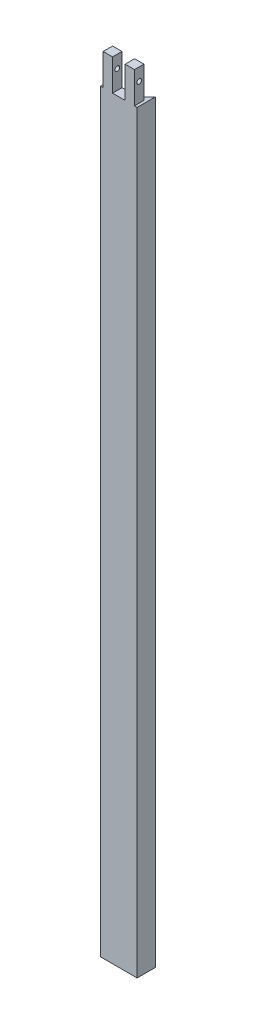
SolidWorks part; units mm, degrees
ref_plane "Front Plane" through (0, 0, 0) normal (0, 0, 1) x (1, 0, 0)
ref_plane "Top Plane" through (0, 0, 0) normal (0, 1, 0) x (1, 0, 0)
ref_plane "Right Plane" through (0, 0, 0) normal (1, 0, 0) x (0, 0, -1)
sketch "Sketch2" plane through (0, 0, 0) normal (0, 0, 1) x (1, 0, 0)
  line L1 (0, 0) -> (-6, 0)
  line L2 (0, 0) -> (0, -240)
  line L3 (0, -240) -> (-6, -240)
  line L4 (-6, 0) -> (-6, -240)
  dimension "D1" = 6
  dimension "D2" = 240
extrude "Boss-Extrude1" add sketch "Sketch2" along normal blind 3
sketch "Sketch4" plane through (0, -240, 0) normal (0, -1, 0) x (-1, 0, 0)
  line L0 (0, 0) -> (-2.8284, 2.8284)
  line L1 (-2.8284, 2.8284) -> (-2.8284, -3)
  line L2 (-2.8284, -3) -> (0, -3)
  line L3 (0, -3) -> (0, 0)
  line L4 (3, 0) -> (3, -3.7119) construction
  line L5 (6, 0) -> (0, 0) construction
  line L6 (8.8284, -3) -> (6, -3)
  line L7 (8.8284, 2.8284) -> (8.8284, -3)
  line L8 (6, 0) -> (8.8284, 2.8284)
  line L9 (6, -3) -> (6, 0)
  dimension "D1" = 135
  dimension "D2" = 4
extrude "Boss-Extrude2" add sketch "Sketch4" against normal up to vertex (240 mm away) up to point (0, 0, 0)
sketch "Sketch5" plane through (0, 0, 0) normal (0, 1, 0) x (1, 0, 0)
  line L0 (2.8284, -3) -> (-8.8284, -3) construction
  line L1 (-8, -3) -> (-5, -3)
  line L2 (-8, -3) -> (-8, 0)
  line L3 (-8, 0) -> (-5, 0)
  line L4 (-5, -3) -> (-5, 0)
  line L5 (-3, 0) -> (-3, -4.0355) construction
  line L6 (0, 0) -> (-6, 0) construction
  line L7 (2, 0) -> (-1, 0)
  line L8 (-1, -3) -> (-1, 0)
  line L9 (2, -3) -> (-1, -3)
  line L10 (2, -3) -> (2, 0)
  dimension "D1" = 3
  dimension "D2" = 2
  dimension "D3" = 0
extrude "Boss-Extrude3" add sketch "Sketch5" along normal blind 10
sketch "Sketch6" plane through (2, 0, 0) normal (1, 0, 0) x (0, 0, -1)
  line L0 (-3, 10) -> (-3, 0) construction
  line L1 (-3, 10) -> (0, 10) construction
  circle A0 centre (-1.5, 6) radius 0.75
  dimension "D1" = 1.5
  dimension "D2" = 1.5
  dimension "D3" = 4
extrude "Cut-Extrude1" cut sketch "Sketch6" against normal blind 40
